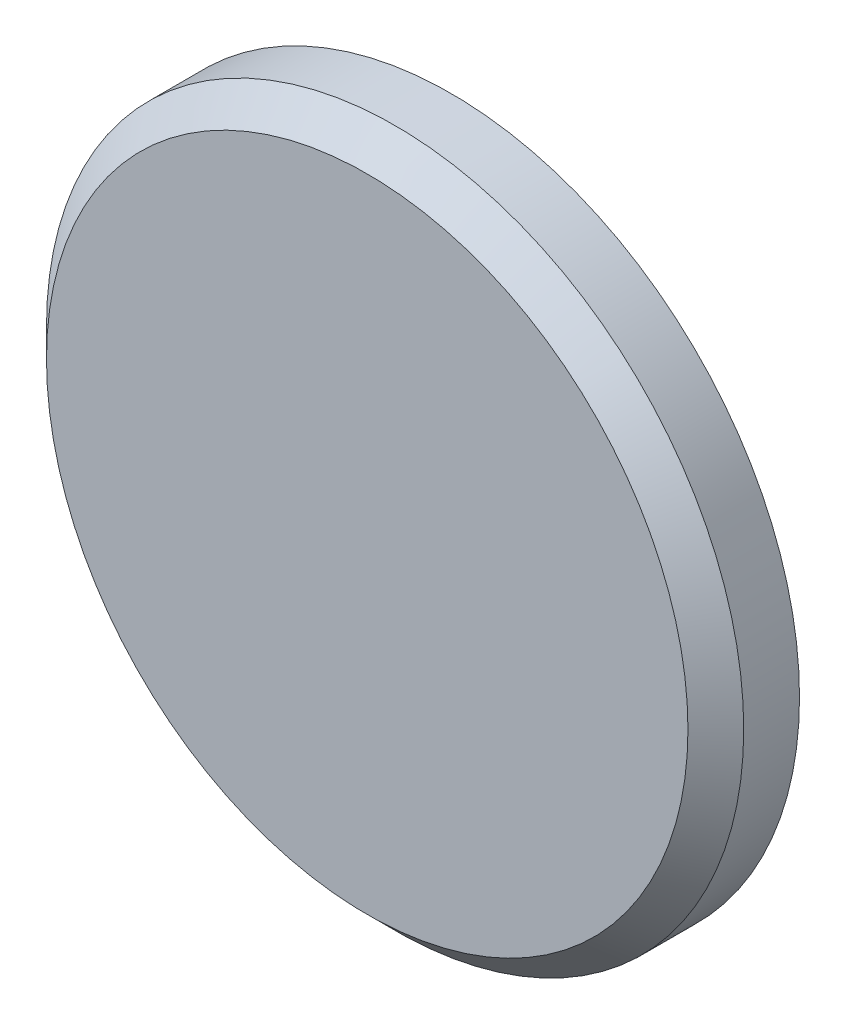
SolidWorks part; units mm, degrees
ref_plane "Front Plane" through (0, 0, 0) normal (0, 0, 1) x (1, 0, 0)
ref_plane "Top Plane" through (0, 0, 0) normal (0, 1, 0) x (1, 0, 0)
ref_plane "Right Plane" through (0, 0, 0) normal (1, 0, 0) x (0, 0, -1)
sketch "Sketch1" plane through (0, 0, 0) normal (0, 0, 1) x (1, 0, 0)
  circle A0 centre (0, 0) radius 12.5
  dimension "D1" = 25
extrude "Corpo" add sketch "Sketch1" against normal blind 3
chamfer "Chanfro 1x45°" distance 1 angle 45 1 edges at (12.5, 0, 0)
